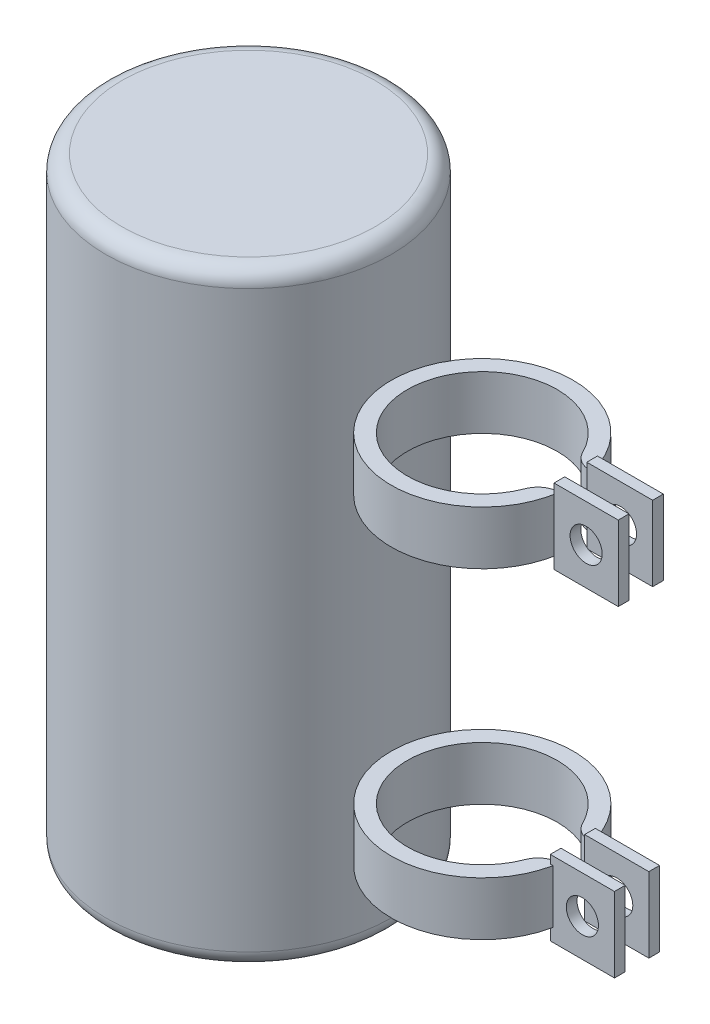
SolidWorks part; units mm, degrees
material "1060 Alloy"
ref_plane "Front Plane" through (0, 0, 0) normal (0, 0, 1) x (1, 0, 0)
ref_plane "Top Plane" through (0, 0, 0) normal (0, 1, 0) x (1, 0, 0)
ref_plane "Right Plane" through (0, 0, 0) normal (1, 0, 0) x (0, 0, -1)
sketch "Sketch1" plane through (0, 0, 0) normal (0, 1, 0) x (1, 0, 0)
  circle A0 centre (0, 0) radius 13.3333
  dimension "D1" = 26.6667
extrude "Boss-Extrude1" add sketch "Sketch1" along normal blind 56.6667
shell "Shell1" thickness 1.5
sketch "Sketch4" plane through (0, 1.5, 0) normal (0, 1, 0) x (1, 0, 0)
  line L0 (-8.2442, -8.4889) -> (8.2442, -8.4889)
  arc A0 (8.2442, -8.4889) -> (-8.2442, -8.4889) centre (0, 0) ccw
extrude "Boss-Extrude2" add sketch "Sketch4" along normal mid plane 1.5 from offset 25
fillet "Fillet1" radius 1.5 6 edges at (0, 56.6667, 13.3333) (0, 1.5, 11.8333) (0, 0, 13.3333) (0, 55.1667, 11.8333) (0, 25.75, -11.8333) (0, 27.25, -11.8333)
sketch "Sketch5" plane through (0, 0, 0) normal (0, 1, 0) x (1, 0, 0)
  circle A1 centre (21.8333, 0) radius 8.5 construction
  circle A2 centre (0, 0) radius 13.3333 construction
  arc A3 (30.0947, 2) -> (30.2467, -1.2103) centre (21.8333, 0) ccw
  arc A4 (28.1076, 3.1037) -> (28.3729, -2.4969) centre (21.8333, 0) ccw
  arc A5 (28.6368, 1.6471) -> (28.762, -0.9967) centre (21.8333, 0) ccw construction
  arc A6 (28.1076, 3.1037) -> (30.0947, 2) centre (29.9003, 3.9905) ccw
  arc A7 (28.3729, -2.4969) -> (30.2467, -1.2103) centre (30.2413, -3.2103) cw
  point P0 (30.0947, 2)
  point P1 (30.0947, -2)
  point P4 (13.3333, 0)
  point P5 (13.3333, 0)
  point P6 (30.3333, 0)
  dimension "D1" = 17
  dimension "D6" = 2
  dimension "D2" = 2
  dimension "D3" = 2
  dimension "D4" = 1.5
extrude "Boss-Extrude3" add sketch "Sketch5" along normal blind 5 from offset 40 separate body contours A3 A7 A4 A6
extrude "Boss-Extrude4" add sketch "Sketch5<3>" along normal blind 5 from offset 10 separate body
sketch "Sketch5<3>" plane through (0, 0, 0) normal (0, 1, 0) x (1, 0, 0) same geometry as "Sketch5"
ref_plane "Plane1" through (0, 0, 1.2103) normal (0, 0, 1) x (0, -1, 0)
sketch "Sketch6" plane through (0, 0, 1.2103) normal (0, 0, 1) x (0, -1, 0)
  line L0 (-46, 30.2467) -> (-46, 36.2467)
  line L2 (-46, 36.2467) -> (-39, 36.2467)
  line L3 (-39, 36.2467) -> (-39, 30.2467)
  line L4 (-39, 30.2467) -> (-39, 36.2467)
  line L5 (-46, 30.2467) -> (-39, 30.2467)
  line L6 (-45, 30.2467) -> (-40, 30.2467) construction
  point P4 (0, 0)
  point P10 (-42.5, 36.2467)
  dimension "D1" = 6
  dimension "D2" = 7
extrude "Boss-Extrude5" add sketch "Sketch6" against normal mid plane 1 separate body contours L0 L5 L3 L2 region at (33.2467, 42.5, 1.2103)
ref_plane "Plane2" through (0, 0, -2) normal (0, 0, 1) x (0, -1, 0)
sketch "Sketch7" plane through (0, 0, -2) normal (0, 0, 1) x (0, -1, 0)
  line L3 (-46, 36.2467) -> (-39, 36.2467)
  line L4 (-39, 36.2467) -> (-39, 30.0947)
  line L5 (-39, 30.0947) -> (-46, 30.0947)
  line L7 (-46, 30.0947) -> (-46, 36.2467)
  line L9 (-45, 30.0947) -> (-40, 30.0947) construction
  line L10 (-45, 30.0947) -> (-40, 30.0947) construction
extrude "Boss-Extrude6" add sketch "Sketch7" along normal mid plane 1 separate body
sketch "Sketch10" plane through (0, 0, 1.2103) normal (0, 0, 1) x (0, -1, 0)
  line L0 (-46, 36.2467) -> (-39, 36.2467) construction
  line L1 (-39, 36.2467) -> (-39, 30.2467) construction
  circle A0 centre (-42.5, 33.2467) radius 1.5
  point P2 (-42.5, 36.2467)
  point P3 (-39, 33.2467)
  point P6 (0, 0)
  point P9 (0, 0)
  dimension "D1" = 3
extrude "Cut-Extrude1" cut sketch "Sketch10" against normal through all both and the other way through all
ref_plane "Plane4" through (0, 0, 1.2103) normal (0, 0, 1) x (0, -1, 0)
ref_plane "Plane5" through (0, 0, -2) normal (0, 0, 1) x (0, -1, 0)
sketch "Sketch14" plane through (0, 1.5, 0) normal (0, 1, 0) x (1, 0, 0)
  circle A0 centre (0, -9.1222) radius 2.5
  dimension "D1" = 5
extrude "Cut-Extrude3" cut sketch "Sketch14" against normal through all from surface contours A0 starting at face at (0, 25.75, -0.9222)
sketch "Sketch17" plane through (0, 0, 1.2103) normal (0, 0, 1) x (0, -1, 0)
  line L0 (-15.7788, 29.8944) -> (-8.7788, 29.8944)
  line L1 (-8.7788, 29.8944) -> (-8.7788, 35.8944)
  line L2 (-8.7788, 35.8944) -> (-15.7788, 35.8944)
  line L3 (-15.7788, 35.8944) -> (-15.7788, 29.8944)
  dimension "D1" = 7
  dimension "D2" = 6
extrude "Boss-Extrude7" add sketch "Sketch17" along normal mid plane 1
sketch "Sketch18" plane through (0, 0, -2) normal (0, 0, 1) x (0, -1, 0)
  line L0 (-15.7788, 35.8944) -> (-15.7788, 29.8944)
  line L2 (-15.7788, 35.8944) -> (-15.7788, 29.8944) construction
  line L3 (-15.7788, 29.8944) -> (-8.7788, 29.8944)
  line L4 (-8.7788, 29.8944) -> (-8.7788, 35.8944)
  line L5 (-8.7788, 35.8944) -> (-15.7788, 35.8944)
  line L6 (-15.7788, 29.8944) -> (-8.7788, 29.8944) construction
extrude "Boss-Extrude8" add sketch "Sketch18" along normal mid plane 1
sketch "Sketch19" plane through (0, 0, 1.7103) normal (0, 0, 1) x (1, 0, 0)
  line L0 (35.8944, 15.7788) -> (29.8944, 15.7788) construction
  line L1 (35.8944, 8.7788) -> (35.8944, 15.7788) construction
  circle A0 centre (32.8944, 12.2788) radius 1.5
  point P0 (32.8944, 15.7788)
  point P1 (35.8944, 12.2788)
  point P8 (0, 0)
  point P9 (0, 0)
  dimension "D1" = 3
extrude "Cut-Extrude4" cut sketch "Sketch19" against normal through all both and the other way through all
